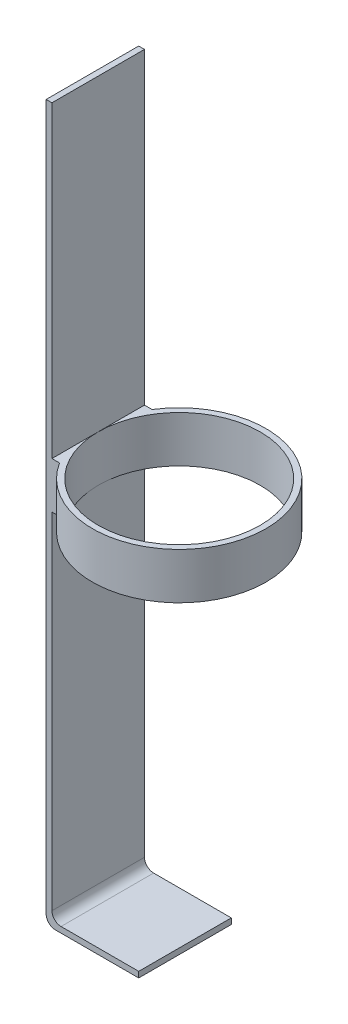
SolidWorks part; units mm, degrees
material "6061-T6 (SS)"
ref_plane "Front Plane" through (0, 0, 0) normal (0, 0, 1) x (1, 0, 0)
ref_plane "Top Plane" through (0, 0, 0) normal (0, 1, 0) x (1, 0, 0)
ref_plane "Right Plane" through (0, 0, 0) normal (1, 0, 0) x (0, 0, -1)
sketch "Sketch1" plane through (0, 0, 0) normal (0, 0, 1) x (1, 0, 0)
  line L1 (0, 0) -> (50.8, 0)
  line L2 (0, 0) -> (0, -387.1625)
  line L3 (5, -392.1625) -> (50.8, -392.1625)
  line L4 (50.8, 0) -> (50.8, -392.1625)
  line L5 (50.8, 0) -> (3.175, 0)
  line L6 (50.8, 0) -> (50.8, -388.9875)
  line L7 (50.8, -388.9875) -> (8.175, -388.9875)
  line L8 (3.175, 0) -> (3.175, -383.9875)
  arc A0 (8.175, -388.9875) -> (3.175, -383.9875) centre (8.175, -383.9875) cw
  arc A1 (0, -387.1625) -> (5, -392.1625) centre (5, -387.1625) ccw
  point P11 (0, -392.1625)
  point P12 (0, 0)
  dimension "D5" = 5
  dimension "D1" = 392.1625
  dimension "D2" = 3.175
  dimension "D3" = 3.175
  dimension "D4" = 50.8
extrude "Boss-Extrude1" add sketch "Sketch1" along normal blind 50.8 contours L2 A1 L3 L4 L7 A0 L8 L1 region at (1.5875, -3.9544, 0)
ref_plane "Plane1" through (0, -194.4938, 0) normal (0, 1, 0) x (1, 0, 0)
sketch "Sketch2" plane through (0, -194.4938, 0) normal (0, 1, 0) x (1, 0, 0)
  line L0 (3.175, -50.8) -> (3.175, 0) construction
  line L1 (0, -50.8) -> (7.3388, -50.8)
  line L2 (3.175, -50.8) -> (8.175, -50.8) construction
  line L3 (0, 0) -> (7.3388, 0)
  line L4 (8.175, 0) -> (3.175, 0) construction
  line L7 (3.175, 0) -> (0, 0)
  line L8 (0, 0) -> (0, -50.8)
  line L9 (0, -50.8) -> (3.175, -50.8)
  line L10 (3.175, -50.8) -> (3.175, 0)
  line L11 (3.175, 0) -> (0, 0)
  line L12 (0, 0) -> (0, -50.8)
  line L13 (0, -50.8) -> (3.175, -50.8)
  line L14 (3.175, -50.8) -> (3.175, 0)
  circle A0 centre (47.625, -25.4) radius 44.45
  circle A1 centre (47.625, -25.4) radius 47.625
  point P3 (3.175, -25.4)
  point P4 (3.175, -25.4)
  dimension "D1" = 88.9
  dimension "D2" = 3.175
  dimension "D3" = 0
extrude "Boss-Extrude3" add sketch "Sketch2" along normal blind 25.4 contours L14 A1 | A1 L14 A0 | A1 L14 L1 | A1 L3 L14 region at (4.5087, -194.4938, 48.1515) region at (1.9013, -194.4938, 25.4) region at (6.2382, -194.4938, 46.1568) region at (4.5087, -194.4938, 2.6485)
